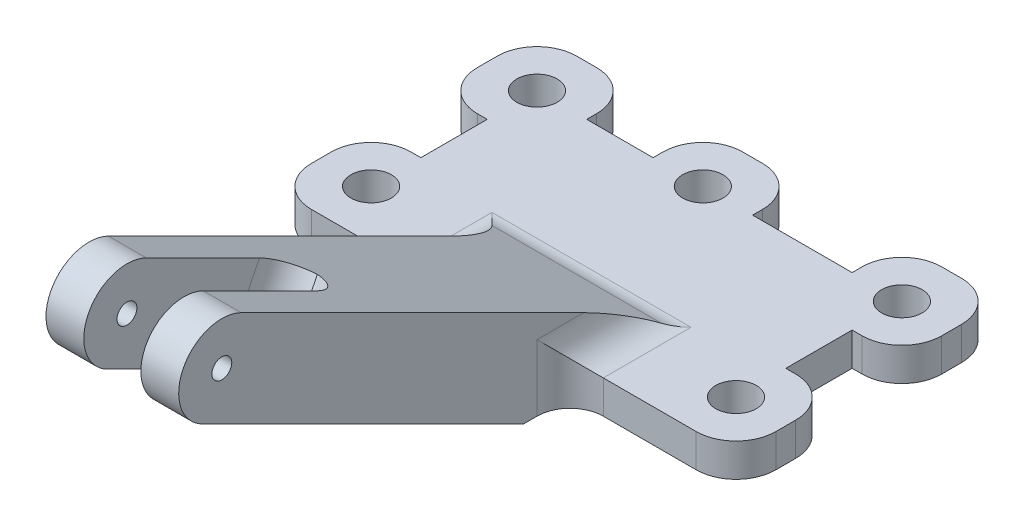
SolidWorks part; units mm, degrees
ref_plane "Front Plane" through (0, 0, 0) normal (0, 0, 1) x (1, 0, 0)
ref_plane "Top Plane" through (0, 0, 0) normal (0, 1, 0) x (1, 0, 0)
ref_plane "Right Plane" through (0, 0, 0) normal (1, 0, 0) x (0, 0, -1)
sketch "Sketch1" plane through (0, 0, 0) normal (1, 0, 0) x (0, 0, -1)
  line L0 (0, 52.532) -> (0, -45.4091) construction
  line L1 (0, 0) -> (60, 0) construction
  line L2 (60, 0) -> (0, 30) construction
  line L3 (2.9069, 35.8138) -> (74.5344, 0)
  line L4 (-2.9069, 24.1862) -> (45.4656, 0)
  line L5 (45.4656, 0) -> (74.5344, 0)
  circle A0 centre (0, 30) radius 1.5
  arc A1 (2.9069, 35.8138) -> (-2.9069, 24.1862) centre (0, 30) ccw
  dimension "D1" = 3
  dimension "D4" = 13
  dimension "D2" = 30
  dimension "D3" = 60
extrude "Boss-Extrude1" add sketch "Sketch1" along normal blind 20
sketch "Sketch2" plane through (0, 29.8138, -14.9069) normal (0, 0.8944, -0.4472) x (1, 0, 0)
  line L0 (10, 66.6656) -> (10, -13.4164) construction
  line L2 (20, -13.4164) -> (0, -13.4164) construction
  line L3 (5.7, 10.6642) -> (14.3, 10.6642)
  line L4 (5.7, 10.6642) -> (5.7, -25.6487)
  line L5 (14.3, 10.6642) -> (14.3, -25.6487)
  line L6 (5.7, -25.6487) -> (14.3, -25.6487)
  point P8 (10, 66.6656)
  dimension "D1" = 8.6
extrude "Cut-Extrude1" cut sketch "Sketch2" against normal blind 20
sketch "Sketch3" plane through (0, 0, 0) normal (0, -1, 0) x (1, 0, 0)
  line L0 (10, -72.5) -> (52.1955, -72.5) construction
  line L1 (10, -72.5) -> (10, -45.4656) construction
  line L2 (20, -45.4656) -> (0, -45.4656) construction
  line L3 (-5, -45.4656) -> (-5, -90.7708) construction
  line L4 (-15, -60) -> (10.9988, -60) construction
  line L5 (-17.5, -60) -> (7.5, -60) construction
  line L6 (-5, -60) -> (-5, -72.5) construction
  line L7 (-24.1112, -72.5) -> (21.9407, -72.5) construction
  line L8 (-17.5, -67.5) -> (10.5654, -67.5) construction
  line L9 (-16, -92.5) -> (-19, -92.5)
  line L11 (-25, -86.5) -> (-25, -83.5)
  line L12 (15, -92.5) -> (-25, -52.5) construction
  line L13 (15, -52.5) -> (-25, -92.5) construction
  line L14 (-17.5, -77.5) -> (10.5654, -77.5) construction
  line L15 (-17.5, -67.5) -> (-17.5, -77.5)
  line L16 (-19, -52.5) -> (-19, -74.9834) construction
  line L17 (-17.5, -67.5) -> (-19, -67.5)
  line L18 (-17.5, -77.5) -> (-19, -77.5)
  line L19 (-25, -61.5) -> (-25, -58.5)
  line L21 (15, -86.5) -> (15, -85)
  line L25 (-17.5, -85) -> (7.5, -85) construction
  line L26 (-10, -85) -> (-10, -86.5)
  line L27 (6, -92.5) -> (9, -92.5)
  line L28 (0, -85) -> (0, -86.5)
  line L29 (-10, -85) -> (0, -85)
  line L30 (39, -52.5) -> (39, -74.9834) construction
  line L31 (25, -60) -> (25, -72.5) construction
  line L32 (30, -85) -> (30, -86.5)
  line L33 (45, -61.5) -> (45, -58.5)
  line L34 (37.5, -77.5) -> (39, -77.5)
  line L35 (37.5, -67.5) -> (39, -67.5)
  line L36 (37.5, -67.5) -> (37.5, -77.5)
  line L37 (45, -86.5) -> (45, -83.5)
  line L38 (36, -92.5) -> (39, -92.5)
  line L40 (30, -85) -> (15, -85)
  line L41 (-17.5, -52.5) -> (-19, -52.5)
  line L42 (37.5, -52.5) -> (39, -52.5)
  line L43 (-17.5, -52.5) -> (37.5, -52.5)
  arc A0 (10, -58.2529) -> (9.6567, -57.8433) centre (7.5, -60) ccw
  circle A1 centre (-17.5, -60) radius 3.05
  circle A2 centre (7.5, -85) radius 3.05
  circle A3 centre (-17.5, -85) radius 3.05
  arc A4 (15, -86.5) -> (9, -92.5) centre (9, -86.5) cw
  arc A6 (-19, -92.5) -> (-25, -86.5) centre (-19, -86.5) cw
  arc A7 (-19, -52.5) -> (-25, -58.5) centre (-19, -58.5) ccw
  circle A8 centre (-17.5, -60) radius 7.5 construction
  arc A9 (-25, -61.5) -> (-19, -67.5) centre (-19, -61.5) ccw
  arc A10 (-25, -83.5) -> (-19, -77.5) centre (-19, -83.5) cw
  circle A13 centre (-17.5, -85) radius 7.5 construction
  arc A14 (-16, -92.5) -> (-10, -86.5) centre (-16, -86.5) ccw
  arc A15 (6, -92.5) -> (0, -86.5) centre (6, -86.5) cw
  circle A16 centre (37.5, -85) radius 7.5 construction
  circle A17 centre (37.5, -60) radius 7.5 construction
  arc A18 (36, -92.5) -> (30, -86.5) centre (36, -86.5) cw
  arc A19 (45, -83.5) -> (39, -77.5) centre (39, -83.5) ccw
  arc A20 (45, -61.5) -> (39, -67.5) centre (39, -61.5) cw
  arc A21 (39, -52.5) -> (45, -58.5) centre (39, -58.5) cw
  arc A22 (39, -92.5) -> (45, -86.5) centre (39, -86.5) ccw
  circle A23 centre (37.5, -85) radius 3.05
  circle A24 centre (37.5, -60) radius 3.05
  point P12 (-5, -60)
  point P47 (-10, -67.5)
  point P50 (-10, -77.5)
  point P96 (30, -77.5)
  point P97 (30, -67.5)
  dimension "D2" = 25
  dimension "D5" = 40
  dimension "D6" = 6
  dimension "D7" = 6
  dimension "D8" = 6
  dimension "D3" = 6.1
  dimension "D9" = 6
  dimension "D1" = 15
  dimension "D4" = 12.5
  dimension "D10" = 40
fillet "Fillet2" radius 5 2 edges at (5.7, 19.2308, -21.5383) (14.3, 19.2308, -21.5383)
extrude "Boss-Extrude3" add sketch "Sketch3" against normal blind 5
fillet "Fillet3" radius 5 3 edges at (0, 5, -58.5172) (20, 5, -58.5172) (10, 5, -64.5344)
fillet "Fillet4" radius 5 2 edges at (0, 5, -52.5) (20, 5, -52.5)
